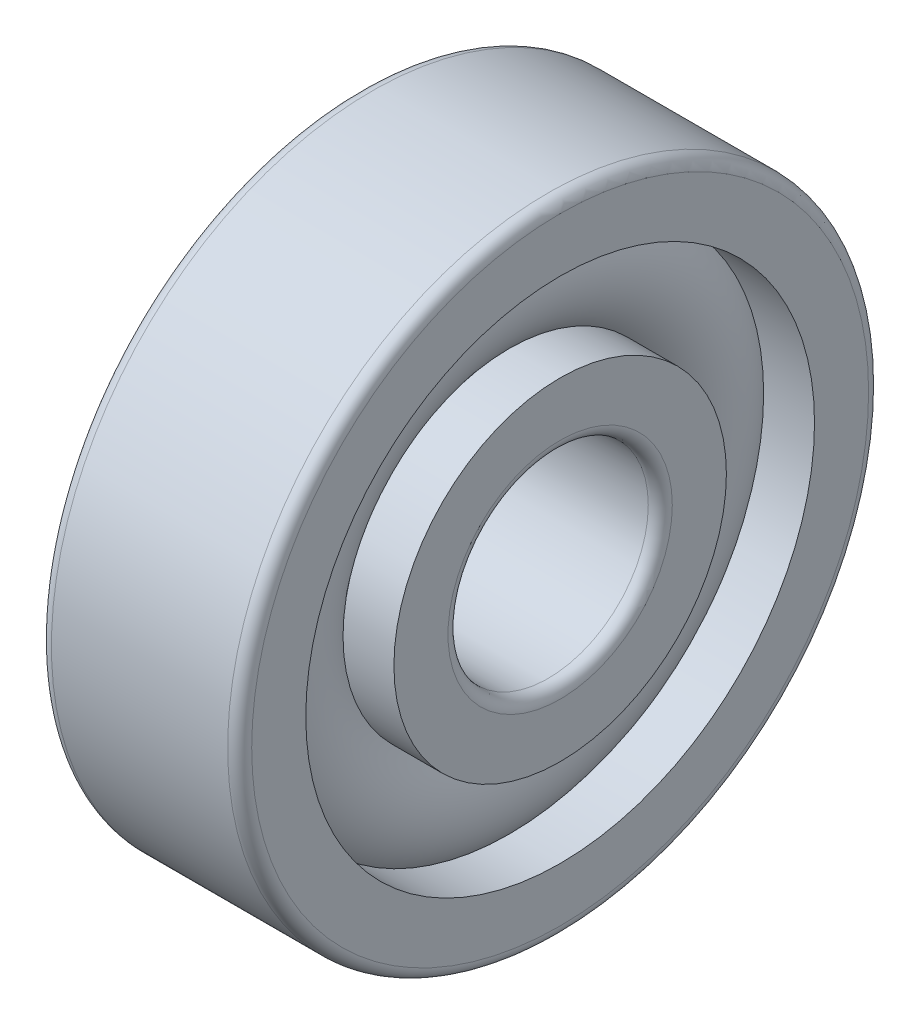
SolidWorks part; units mm, degrees
ref_plane "Plane1" through (0, 0, 0) normal (0, 0, 1) x (1, 0, 0)
ref_plane "Plane2" through (0, 0, 0) normal (0, 1, 0) x (1, 0, 0)
ref_plane "Plane3" through (0, 0, 0) normal (1, 0, 0) x (0, 0, -1)
sketch "Clipboard" plane through (0, 0, 0) normal (0, 0, 1) x (1, 0, 0)
  line L0 (-10, 0) -> (10, 0) construction
  line L1 (0, 0) -> (22.3471, -0.7804)
  line L2 (0, 0) -> (5.2468, 0.1832)
  line L3 (0, 0) -> (22.3471, -0.7804)
  line L4 (0, 0) -> (-22.3573, -0.3902)
  dimension "BallCLRad" = 5.25
  dimension "Count" = 2
  dimension "Show_count" = 2
  dimension "Max_count" = 2
  dimension "Min_count" = 1
sketch "CagSpiSke" plane through (0, 0, 0) normal (0, 0, 1) x (1, 0, 0)
  line L0 (0.165, 4.975) -> (0.165, 5.525)
  line L1 (0.165, 5.525) -> (-0.165, 5.525)
  line L2 (-0.165, 5.525) -> (-0.165, 4.975)
  line L3 (-0.165, 4.975) -> (0.165, 4.975)
  line L4 (-20.6375, 0) -> (20.6375, 0) construction
  line L5 (0, 0) -> (0, 23.7692) construction
  dimension "Thickness" = 0.33
  dimension "OD" = 11.05
  dimension "ID" = 9.95
revolve "CageSpine" add sketch "CagSpiSke" angle 0.001 about L4 reverse direction yes
ref_axis "Axis1" through (-50, 0, 0) along (1, 0, 0)
sketch "CagBalSke" plane through (0, 0, 0) normal (0, 0, 1) x (1, 0, 0)
  line L0 (-1.815, 5.25) -> (1.815, 5.25)
  line L1 (-1.905, 5.25) -> (1.905, 5.25) construction
  line L2 (-10, 0) -> (10, 0) construction
  line L3 (0, 0) -> (0, 24) construction
  arc A0 (1.815, 5.25) -> (-1.815, 5.25) centre (0, 5.25) cw
  dimension "CageWallOD" = 3.63
  dimension "BallCLRad" = 5.25
revolve "CageBall" [suppressed] add sketch "CagBalSke" angle 360 about L1 reverse direction yes
pattern_circular "CageBalls" [suppressed] count 2 every 180 about axis through (-50, 0, 0) along (1, 0, 0)
sketch "CagTrmODSke" plane through (0, 0, 0) normal (0, 0, 1) x (1, 0, 0)
  line L0 (1.816, 5.525) -> (1.816, 7.066)
  line L1 (1.816, 7.066) -> (-1.816, 7.066)
  line L2 (-1.816, 7.066) -> (-1.816, 5.525)
  line L3 (-1.816, 5.525) -> (1.816, 5.525)
  line L4 (-20.6375, 0) -> (20.6375, 0) construction
  line L5 (0, 0) -> (0, 25) construction
  dimension "Width" = 3.632
  dimension "ID" = 11.05
  dimension "OD" = 14.132
revolve "CageTrimOD" [suppressed] cut sketch "CagTrmODSke" angle 360 about L4 reverse direction yes
sketch "CagTrmIDSke" plane through (0, 0, 0) normal (0, 0, 1) x (1, 0, 0)
  line L0 (1.816, 3.436) -> (1.816, 4.975)
  line L1 (1.816, 4.975) -> (-1.816, 4.975)
  line L2 (-1.816, 4.975) -> (-1.816, 3.436)
  line L3 (-1.816, 3.436) -> (1.816, 3.436)
  line L4 (-20.6375, 0) -> (20.6375, 0) construction
  line L5 (0, 0) -> (0, 25) construction
  dimension "ID" = 6.872
  dimension "OD" = 9.95
  dimension "Width" = 3.632
revolve "CageTrimID" [suppressed] cut sketch "CagTrmIDSke" angle 360 about L4 reverse direction yes
sketch "BalSimSke" plane through (0, 0, 0) normal (0, 0, 1) x (1, 0, 0)
  line L0 (-10, 0) -> (10, 0) construction
  line L1 (-10, 5.25) -> (10, 5.25) construction
  line L2 (0, 0) -> (0, 23) construction
  circle A0 centre (0, 5.25) radius 1.65
  dimension "Ball_diameter" = 3.3
  dimension "BallCLRad" = 5.25
revolve "BallsSimplified" add sketch "BalSimSke" angle 360 about L0
sketch "BalDetSke" plane through (0, 0, 0) normal (0, 0, 1) x (1, 0, 0)
  line L0 (-1.65, 5.25) -> (1.65, 5.25)
  line L1 (-1.905, 5.25) -> (1.905, 5.25) construction
  line L2 (0, 0) -> (0, 25) construction
  arc A0 (1.65, 5.25) -> (-1.65, 5.25) centre (0, 5.25) cw
  dimension "Ball_diameter" = 3.3
  dimension "BallCLRad" = 5.25
revolve "BallDetailed" [suppressed] add sketch "BalDetSke" angle 360 about L1 reverse direction yes
sketch "InnRacSke" plane through (0, 0, 0) normal (0, 0, 1) x (1, 0, 0)
  line L0 (-1.1961, 4.15) -> (-2.5, 4.15)
  line L1 (-2.5, 4.15) -> (-2.5, 2.8)
  line L2 (-2.2, 2.5) -> (2.2, 2.5)
  line L3 (2.5, 2.8) -> (2.5, 4.15)
  line L4 (2.5, 4.15) -> (1.1961, 4.15)
  line L5 (-20.6375, 0) -> (20.6375, 0) construction
  line L6 (0, 0) -> (0, 30) construction
  arc A0 (-2.5, 2.8) -> (-2.2, 2.5) centre (-2.2, 2.8) ccw
  arc A1 (2.2, 2.5) -> (2.5, 2.8) centre (2.2, 2.8) ccw
  arc A2 (1.1961, 4.15) -> (-1.1961, 4.15) centre (0, 5.25) cw
  dimension "Fillet_radius" = 0.3
  dimension "Ball_diameter" = 3.25
  dimension "ID" = 5
  dimension "OD" = 8.3
  dimension "Width" = 5
  dimension "BallCLRad" = 5.25
revolve "InnerRace" add sketch "InnRacSke" angle 360 about L5 reverse direction yes
sketch "OutRacSke" plane through (0, 0, 0) normal (0, 0, 1) x (1, 0, 0)
  line L0 (-1.1961, 6.35) -> (-2.5, 6.35)
  line L1 (-2.5, 6.35) -> (-2.5, 7.7)
  line L2 (-2.2, 8) -> (2.2, 8)
  line L3 (2.5, 7.7) -> (2.5, 6.35)
  line L4 (2.5, 6.35) -> (1.1961, 6.35)
  line L5 (-20.6375, 0) -> (20.6375, 0) construction
  line L6 (0, 0) -> (0, 30) construction
  arc A0 (-2.5, 7.7) -> (-2.2, 8) centre (-2.2, 7.7) cw
  arc A1 (2.2, 8) -> (2.5, 7.7) centre (2.2, 7.7) cw
  arc A2 (1.1961, 6.35) -> (-1.1961, 6.35) centre (0, 5.25) ccw
  dimension "Fillet_radius" = 0.3
  dimension "Ball_diameter" = 3.25
  dimension "OD" = 16
  dimension "ID" = 12.7
  dimension "Width" = 5
  dimension "BallCLRad" = 5.25
revolve "OuterRace" add sketch "OutRacSke" angle 360 about L5 reverse direction yes
pattern_circular "BallsDetailed" [suppressed] count 2 every 180 about axis through (-50, 0, 0) along (1, 0, 0)
equation "\"BallCLRad@Clipboard\" = ( \"OD@OutRacSke\" + \"ID@InnRacSke\" ) / 4"
equation "\"BallCLRad@BalSimSke\" = \"BallCLRad@Clipboard\""
equation "\"BallCLRad@BalDetSke\" = \"BallCLRad@Clipboard\""
equation "\"BallCLRad@InnRacSke\" = \"BallCLRad@Clipboard\""
equation "\"BallCLRad@OutRacSke\" = \"BallCLRad@Clipboard\""
equation "\"Ball_diameter@InnRacSke\" = \"Ball_diameter@BalDetSke\" - 0.05"
equation "\"Ball_diameter@OutRacSke\" = \"Ball_diameter@BalDetSke\" - 0.05"
equation "\"Ball_diameter@BalSimSke\" = \"Ball_diameter@BalDetSke\""
equation "\"Width@OutRacSke\" = \"Width@InnRacSke\""
equation "\"Fillet_radius@OutRacSke\" = \"Fillet_radius@InnRacSke\""
equation "\"Max_count@Clipboard\" = int( 3.14159265 / atn(( \"Ball_diameter@BalDetSke\" / 2) / sqr( \"BallCLRad@Clipboard\"  *  \"BallCLRad@Clipboard\" - ( \"Ball_diameter@BalDetSke\" / 2) *  ( \"Ball_diameter@BalDetSke\" / 2))))"
equation "\"Max_count@Clipboard\" = ((sgn( \"Max_count@Clipboard\" - \"Count@Clipboard\" )-1)*( \"Max_count@Clipboard\" - \"Count@Clipboard\" ))/-2+ \"Count@Clipboard\""
equation "\"Count@BallsDetailed\" = int( \"Show_count@Clipboard\" ) "
equation "\"Count@BallsDetailed\" = ((sgn( \"Count@BallsDetailed\" - \"Max_count@Clipboard\" )-1)*( \"Count@BallsDetailed\" - \"Max_count@Clipboard\" ))/-2+ \"Max_count@Clipboard\""
equation "\"Count@BallsDetailed\" = ((sgn( \"Count@BallsDetailed\" - \"Min_count@Clipboard\" )+1)*( \"Count@BallsDetailed\" - \"Min_count@Clipboard\"))/2 +\"Min_count@Clipboard\""
equation "\"Angle@BallsDetailed\" = 360.0 / \"Max_count@Clipboard\""
equation "\"BallCLRad@CagBalSke\" = \"BallCLRad@Clipboard\""
equation "\"Count@CageBalls\" = \"Count@BallsDetailed\""
equation "\"Angle@CageBalls\" = \"Angle@BallsDetailed\""
equation "\"Angle@CageSpine\" =  \"Angle@CageBalls\" * ( \"Count@CageBalls\" -1 + int( \"Count@CageBalls\" / \"Max_count@Clipboard\" ) )  + 0.001 -  int( \"Count@CageBalls\" / \"Max_count@Clipboard\" ) * 0.001"
equation "\"Angle@CageSpine\" =  \"Angle@CageSpine\" * int( \"Min_count@Clipboard\" / 2) + int(1 / \"Min_count@Clipboard\")  * 0.001"
equation "\"CageWallOD@CagBalSke\" =  \"Ball_diameter@BalDetSke\" * 1.1"
equation "\"Thickness@CagSpiSke\" =  \"Ball_diameter@BalDetSke\" * 0.1"
equation "\"OD@CagTrmODSke\" = \"BallCLRad@Clipboard\" * 2 + \"CageWallOD@CagBalSke\" + 0.002"
equation "\"ID@CagTrmODSke\" = \"BallCLRad@Clipboard\" * 2 + \"Ball_diameter@BalDetSke\" / 6"
equation "\"OD@CagTrmIDSke\" = \"BallCLRad@Clipboard\" * 2 - \"Ball_diameter@BalDetSke\" / 6"
equation "\"ID@CagTrmIDSke\" = \"BallCLRad@Clipboard\" * 2 - \"CageWallOD@CagBalSke\" + 0.002"
equation "\"OD@CagSpiSke\" = \"ID@CagTrmODSke\""
equation "\"ID@CagSpiSke\" = \"OD@CagTrmIDSke\""
equation "\"Width@CagTrmODSke\" = \"CageWallOD@CagBalSke\" + 0.002"
equation "\"Width@CagTrmIDSke\" = \"CageWallOD@CagBalSke\" + 0.002"
